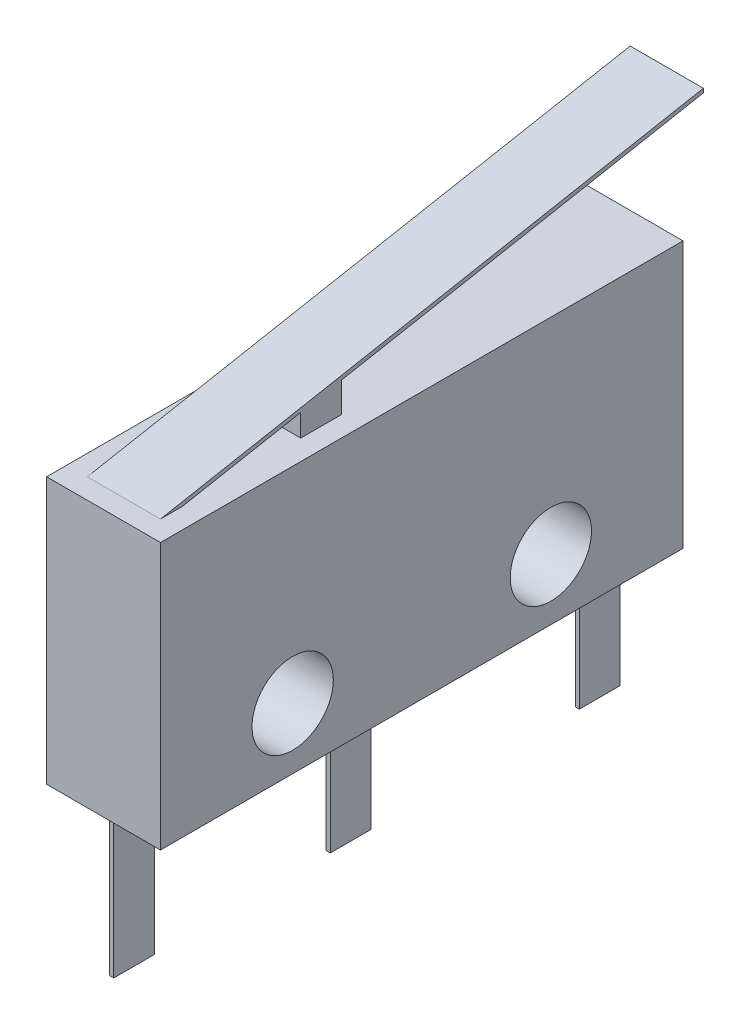
SolidWorks part; units mm, degrees
ref_plane "Front Plane" through (0, 0, 0) normal (0, 0, 1) x (1, 0, 0)
ref_plane "Top Plane" through (0, 0, 0) normal (0, 1, 0) x (1, 0, 0)
ref_plane "Right Plane" through (0, 0, 0) normal (1, 0, 0) x (0, 0, -1)
sketch "BodySketch1" plane through (0, 0, 0) normal (1, 0, 0) x (0, 0, -1)
  line L1 (0, 0) -> (12.85, 0)
  line L2 (0, 0) -> (0, 6.55)
  line L3 (0, 6.55) -> (12.85, 6.55)
  line L4 (12.85, 0) -> (12.85, 6.55)
  circle A0 centre (3.25, 1.5) radius 1
  circle A1 centre (9.6, 1.5) radius 1
  dimension "D6" = 2
  dimension "D1" = 12.85
  dimension "D2" = 6.55
  dimension "D3" = 1.5
  dimension "D4" = 3.25
  dimension "D5" = 3.25
extrude "BodyBoss-Extrude1" add sketch "BodySketch1" along normal blind 2.8
sketch "Sketch2" plane through (0, 6.55, 0) normal (0, 1, 0) x (1, 0, 0)
  line L0 (2.8, 12.85) -> (2.8, 0) construction
  line L1 (0.5, 0.5) -> (2.3, 0.5)
  line L2 (0.5, 0.5) -> (0.5, 13.85)
  line L3 (0.5, 13.85) -> (2.3, 13.85)
  line L4 (2.3, 0.5) -> (2.3, 13.85)
  line L5 (0, 12.85) -> (0, 0) construction
  line L6 (2.8, 0) -> (0, 0) construction
  line L7 (2.8, 12.85) -> (0, 12.85) construction
  dimension "D1" = 0.5
  dimension "D2" = 0.5
  dimension "D3" = 0.5
  dimension "D4" = 1
extrude "LeverBoss-Extrude2" add sketch "Sketch2" along normal blind 2.5
sketch "Sketch3" plane through (2.3, 0, 0) normal (1, 0, 0) x (0, 0, -1)
  line L0 (0.5, 6.55) -> (13.85, 9.05)
  line L1 (13.85, 9.05) -> (13.85, 6.55) construction
  line L2 (0.5, 9.05) -> (13.85, 9.05) construction
  line L3 (13.85, 9.05) -> (0.5, 9.05)
  line L4 (0.5, 9.05) -> (0.5, 6.55)
  line L5 (13.85, 8.95) -> (13.85, 6.55)
  line L6 (13.85, 6.55) -> (1.034, 6.55)
  line L7 (12.85, 6.55) -> (0, 6.55) construction
  line L8 (1.034, 6.55) -> (13.85, 8.95)
  dimension "D1" = 0.1
extrude "LeverCut-Extrude1" cut sketch "Sketch3" against normal through all
sketch "Sketch4" plane through (0, 6.55, 0) normal (0, 1, 0) x (1, 0, 0)
  line L0 (0.5, 0.5) -> (0.5, 13.85) construction
  line L1 (0.5, 4.9489) -> (2.3, 4.9489)
  line L2 (0.5, 4.9489) -> (0.5, 3.9489)
  line L3 (0.5, 3.9489) -> (2.3, 3.9489)
  line L4 (2.3, 4.9489) -> (2.3, 3.9489)
  line L5 (2.3, 0.5) -> (2.3, 13.85) construction
  dimension "D1" = 1
extrude "ButtonBoss-Extrude3" add sketch "Sketch4" along normal up to next
sketch "Sketch5" plane through (0, 0, 0) normal (0, -1, 0) x (1, 0, 0)
  line L0 (2.8, 0) -> (2.8, -12.85) construction
  line L1 (1.35, -0.2) -> (1.45, -0.2)
  line L2 (1.35, -0.2) -> (1.35, -1.2)
  line L3 (1.35, -1.2) -> (1.45, -1.2)
  line L4 (1.45, -0.2) -> (1.45, -1.2)
  line L5 (1.35, -5.525) -> (1.45, -5.525)
  line L6 (1.35, -5.525) -> (1.35, -6.525)
  line L7 (1.35, -6.525) -> (1.45, -6.525)
  line L8 (1.45, -5.525) -> (1.45, -6.525)
  line L9 (1.35, -11.65) -> (1.45, -11.65)
  line L10 (1.35, -11.65) -> (1.35, -12.65)
  line L11 (1.35, -12.65) -> (1.45, -12.65)
  line L12 (1.45, -11.65) -> (1.45, -12.65)
  line L13 (2.8, 0) -> (0, 0) construction
  line L14 (2.8, -12.85) -> (0, -12.85) construction
  line L15 (0, 0) -> (0, -12.85) construction
  dimension "D1" = 0.1
  dimension "D2" = 1.35
  dimension "D4" = 0.2
  dimension "D5" = 0.2
  dimension "D6" = 6.325
extrude "TereminalBoss-Extrude4" add sketch "Sketch5" along normal blind 3.5
equation "\"MicroSwitchLength\"= 12.85mm"
equation "\"D1@BodySketch1\" = \"MicroSwitchLength\""
equation "\"MicroSwitchHeight\"= 6.55mm"
equation "\"D2@BodySketch1\" = \"MicroSwitchHeight\""
equation "\"MicroSwitchMountHoleOffsetFromBottom\"= 1.5mm"
equation "\"MicroSwitchMountHoleOffsetFromSide\"= 3.25mm"
equation "\"D4@BodySketch1\" = \"MicroSwitchMountHoleOffsetFromSide\""
equation "\"D5@BodySketch1\" = \"MicroSwitchMountHoleOffsetFromSide\""
equation "\"MicroSwitchMountHoleDiameter\"= 2mm"
equation "\"D6@BodySketch1\" = \"MicroSwitchMountHoleDiameter\""
equation "\"MicroSwitchDepth\"= 2.8mm"
equation "\"D1@BodyBoss-Extrude1\" = \"MicroSwitchDepth\""
equation "\"MicroSwitchLeverHeight\"= 2.5mm"
equation "\"D1@LeverBoss-Extrude2\" = \"MicroSwitchLeverHeight\""
equation "\"D2@Sketch5\"=(\"MicroSwitchDepth\"-.1)/2"
equation "\"D6@Sketch5\"=(\"MicroSwitchLength\" -.2)/2"
equation "\"MicroSwitchTerminalHeight\"= 3.5mm"
equation "\"D1@TereminalBoss-Extrude4\" = \"MicroSwitchTerminalHeight\""
equation "\"MicroSwitchTerminalWidth\"= .2mm"
equation "\"MicroSwitchTerminalDepth\"= .1mm"
equation "\"D1@Sketch5\"=\"MicroSwitchTerminalDepth\""
equation "\"MicroSwitchLeverDepth\"= .1mm"
equation "\"D1@Sketch3\"=\"MicroSwitchLeverDepth\""
equation "\"D3@BodySketch1\"=\"MicroSwitchMountHoleOffsetFromBottom\""
equation "\"D5@Sketch5\"=\"MicroSwitchTerminalWidth\""
